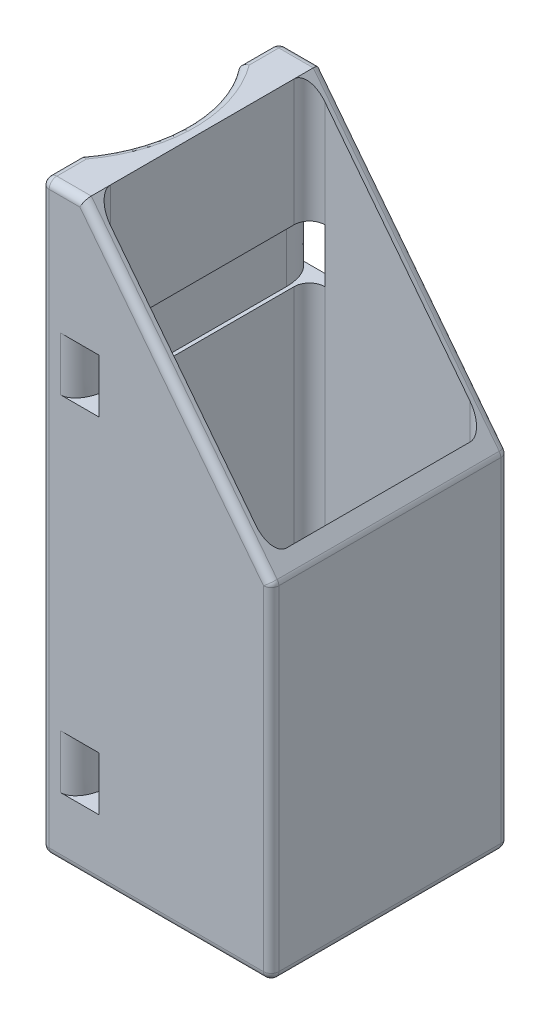
SolidWorks part; units mm, degrees
ref_plane "Front Plane" through (0, 0, 0) normal (0, 0, 1) x (1, 0, 0)
ref_plane "Top Plane" through (0, 0, 0) normal (0, 1, 0) x (1, 0, 0)
ref_plane "Right Plane" through (0, 0, 0) normal (1, 0, 0) x (0, 0, -1)
sketch "Sketch1" plane through (0, 0, 0) normal (0, 1, 0) x (1, 0, 0)
  line L1 (0, 0) -> (30, 0)
  line L3 (0, 31) -> (30, 31)
  line L4 (30, 0) -> (30, 31)
  line L5 (5.5, 1.5) -> (28.5, 1.5)
  line L6 (5.5, 1.5) -> (5.5, 29.5)
  line L7 (5.5, 29.5) -> (28.5, 29.5)
  line L8 (28.5, 1.5) -> (28.5, 29.5)
  line L9 (0, 31) -> (0, 25.7981)
  line L11 (0, 0) -> (0, 5.2019)
  arc A0 (0, 5.2019) -> (0, 25.7981) centre (-13.4, 15.5) ccw
  point P13 (28.5, 15.5)
  point P18 (30, 15.5)
  dimension "D5" = 16.9
  dimension "D6" = 18.9
  dimension "D1" = 1.5
  dimension "D2" = 1.5
  dimension "D3" = 23
  dimension "D4" = 28
  dimension "D7" = 5.5
extrude "Boss-Extrude1" add sketch "Sketch1" along normal blind 75
sketch "Sketch2" plane through (0, 0, 0) normal (0, -1, 0) x (1, 0, 0)
  line L0 (0, -25.7981) -> (0, -31)
  line L1 (0, 0) -> (30, 0)
  line L2 (0, 0) -> (0, -5.2019)
  line L3 (0, -31) -> (30, -31)
  line L4 (30, 0) -> (30, -31)
  arc A0 (0, -25.7981) -> (0, -5.2019) centre (-13.1475, -15.5) ccw
extrude "Boss-Extrude2" add sketch "Sketch2" along normal blind 1.5
sketch "Sketch6" plane through (0, 0, 0) normal (0, 0, 1) x (1, 0, 0)
  line L0 (5.5, 75) -> (30, 43.5)
  line L1 (0, 75) -> (30, 75) construction
  line L2 (30, 75) -> (30, -1.5) construction
  line L3 (30, 43.5) -> (30, 75)
  line L4 (30, 75) -> (5.5, 75)
  dimension "D1" = 5.5
  dimension "D2" = 45
extrude "Cut-Extrude1" cut sketch "Sketch6" against normal through all
fillet "Fillet1" radius 1 18 edges at (2.75, 75, -31) (15, -1.5, -31) (30, 21, -31) (30, -1.5, -15.5) (2.75, 75, 0) (30, 21, 0) (15, -1.5, 0) (0, -1.5, -2.601) (0, -1.5, -28.399) (0, 36.75, -31) (17.75, 59.25, -31) (30, 43.5, -15.5) (0, 36.75, 0) (17.75, 59.25, 0) (3.553, -1.5, -15.5) (3.5, 75, -15.5) (0, 75, -2.601) (0, 75, -28.399)
sketch "Sketch7" plane through (0, 0, 0) normal (0, 0, 1) x (1, 0, 0)
  line L0 (0, -0.5) -> (0, 74) construction
  line L1 (5.5, 58.5) -> (7.5, 58.5)
  line L2 (5.5, 58.5) -> (5.5, 51.5)
  line L3 (5.5, 51.5) -> (7.5, 51.5)
  line L4 (7.5, 58.5) -> (7.5, 51.5)
  line L5 (5.5, 6.5) -> (7.5, 6.5)
  line L6 (5.5, 6.5) -> (5.5, 13.5)
  line L7 (5.5, 13.5) -> (7.5, 13.5)
  line L8 (7.5, 6.5) -> (7.5, 13.5)
  line L9 (29, -1.5) -> (1, -1.5) construction
  point P12 (6.5, 13.5)
  dimension "D1" = 7
  dimension "D2" = 2
  dimension "D3" = 5.5
  dimension "D4" = 8
  dimension "D5" = 38
extrude "Cut-Extrude2" cut sketch "Sketch7" against normal through all
sketch "Sketch8" plane through (5.5, 0, 0) normal (1, 0, 0) x (0, 0, -1)
  line L1 (31, 51.5) -> (0, 51.5)
  line L2 (31, 51.5) -> (31, 58.5)
  line L3 (31, 58.5) -> (0, 58.5)
  line L4 (0, 51.5) -> (0, 58.5)
  line L5 (0, 6.5) -> (31, 6.5)
  line L6 (0, 6.5) -> (0, 13.5)
  line L7 (0, 13.5) -> (31, 13.5)
  line L8 (31, 6.5) -> (31, 13.5)
extrude "Cut-Extrude3" cut sketch "Sketch8" against normal blind 0.5
fillet "Fillet2" radius 2.5 4 edges at (5, 10, -31) (5, 10, 0) (5, 55, -31) (5, 55, 0) second distance 4 first distance on face at (6.25, 10, -31) first distance on face at (6.25, 55, 0)
fillet "Fillet3" radius 2 12 edges at (17, 0, -29.5) (5.5, 3.25, -29.5) (5.5, 0, -15.5) (5.5, 3.25, -1.5) (17, 0, -1.5) (28.5, 0, -15.5) (28.5, 22.7143, -1.5) (28.5, 22.7143, -29.5) (5.5, 66.75, -1.5) (5.5, 32.5, -1.5) (5.5, 66.75, -29.5) (5.5, 32.5, -29.5)
